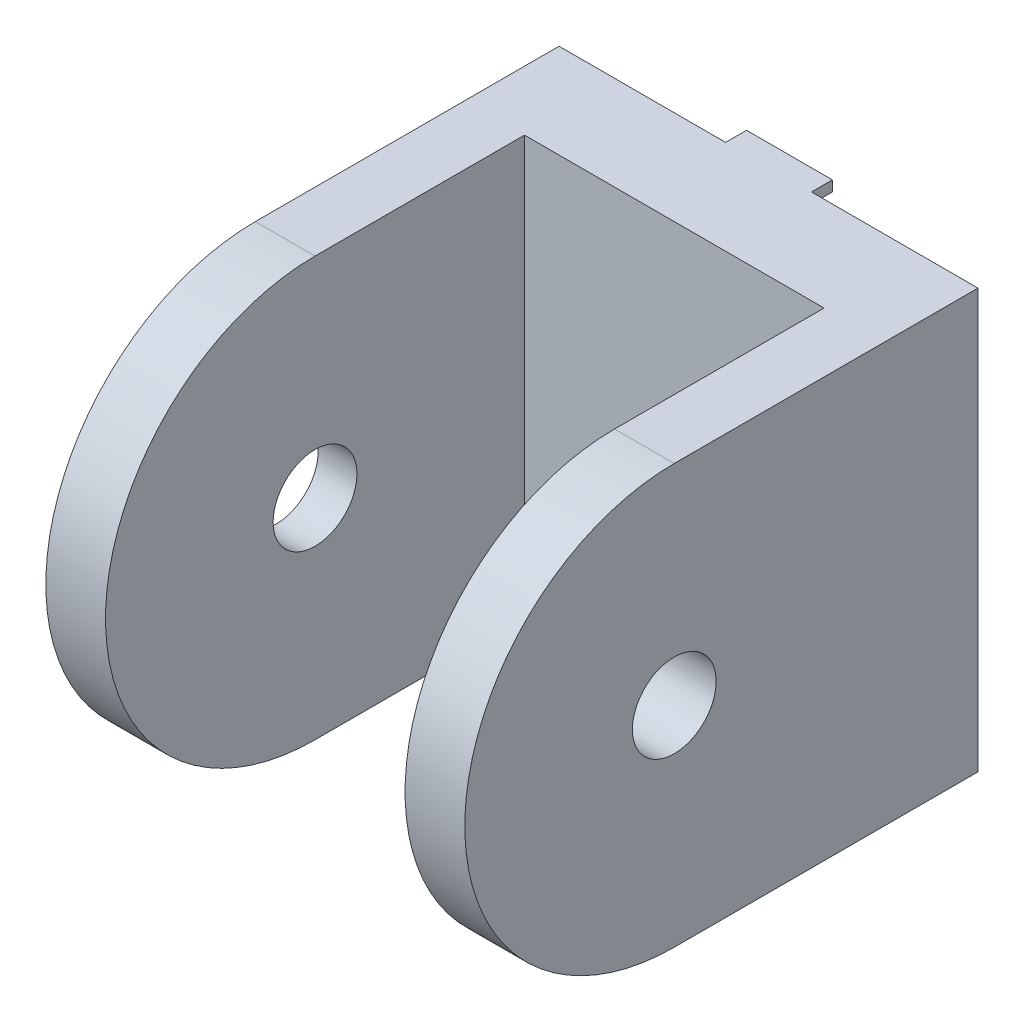
SolidWorks part; units mm, degrees
ref_plane "前视基准面" through (0, 0, 0) normal (0, 0, 1) x (1, 0, 0)
ref_plane "上视基准面" through (0, 0, 0) normal (0, 1, 0) x (1, 0, 0)
ref_plane "右视基准面" through (0, 0, 0) normal (1, 0, 0) x (0, 0, -1)
sketch "草图1" plane through (0, 0, 0) normal (0, 0, 1) x (1, 0, 0)
  line L1 (-20, -20) -> (20, -20)
  line L2 (-20, -20) -> (-20, 20)
  line L3 (-20, 20) -> (20, 20)
  line L4 (20, -20) -> (20, 20)
  line L5 (-20, -20) -> (20, 20) construction
  line L6 (-20, 20) -> (20, -20) construction
  point P0 (0, 0)
  dimension "D1" = 40
  dimension "D2" = 40
extrude "凸台-拉伸1" add sketch "草图1" along normal blind 9
sketch "草图2" plane through (0, 0, 9) normal (0, 0, 1) x (1, 0, 0)
  line L0 (20, 20) -> (-20, 20) construction
  line L1 (-20, -20) -> (-14.3, -20)
  line L2 (-20, -20) -> (-20, 20)
  line L3 (-20, 20) -> (-14.3, 20)
  line L4 (-14.3, -20) -> (-14.3, 20)
  line L5 (0, 0) -> (0, 12.8397) construction
  line L6 (20, -20) -> (14.3, -20)
  line L7 (20, -20) -> (20, 20)
  line L8 (14.3, -20) -> (14.3, 20)
  line L9 (20, 20) -> (14.3, 20)
  dimension "D1" = 5.7
extrude "凸台-拉伸2" add sketch "草图2" along normal blind 40
sketch "草图3" plane through (-20, 0, 0) normal (-1, 0, 0) x (0, 0, 1)
  line L0 (49, 20) -> (49, -20) construction
  line L1 (49, 20) -> (0, 20) construction
  line L2 (29, -20) -> (29, 20) construction
  arc A0 (29, -20) -> (29, 20) centre (29, 0) ccw
  dimension "D1" = 40
extrude "切除-拉伸2" cut sketch "草图3" against normal through all and the other way through all flip side to cut
sketch "草图4" plane through (-20, 0, 0) normal (-1, 0, 0) x (0, 0, 1)
  circle A0 centre (29, 0) radius 4
  dimension "D1" = 8
extrude "切除-拉伸3" cut sketch "草图4" against normal through all
sketch "草图5" plane through (-20, 0, 0) normal (-1, 0, 0) x (0, 0, 1)
  circle A0 centre (29, 0) radius 8
  dimension "D1" = 16
extrude "切除-拉伸4" cut sketch "草图5" against normal blind 2
sketch "草图6" plane through (0, 0, 9) normal (0, 0, 1) x (1, 0, 0)
  circle A0 centre (0, 0) radius 4
  dimension "D1" = 8
extrude "切除-拉伸5" cut sketch "草图6" against normal through all
sketch "草图7" plane through (0, 0, 0) normal (0, 0, -1) x (-1, 0, 0)
  line L0 (-20, 20) -> (20, 20) construction
  line L1 (-4.1, 20) -> (4.1, 20)
  line L2 (-4.1, 20) -> (-4.1, 19)
  line L3 (-4.1, 19) -> (4.1, 19)
  line L4 (4.1, 20) -> (4.1, 19)
  line L5 (0, 0) -> (-9.0525, 0) construction
  line L6 (4.1, -20) -> (4.1, -19)
  line L7 (-4.1, -20) -> (-4.1, -19)
  line L8 (-4.1, -19) -> (4.1, -19)
  line L9 (-4.1, -20) -> (4.1, -20)
  point P9 (0, 20)
  point P10 (0, 20)
  dimension "D1" = 8.2
  dimension "D2" = 1
extrude "凸台-拉伸3" add sketch "草图7" along normal blind 2
